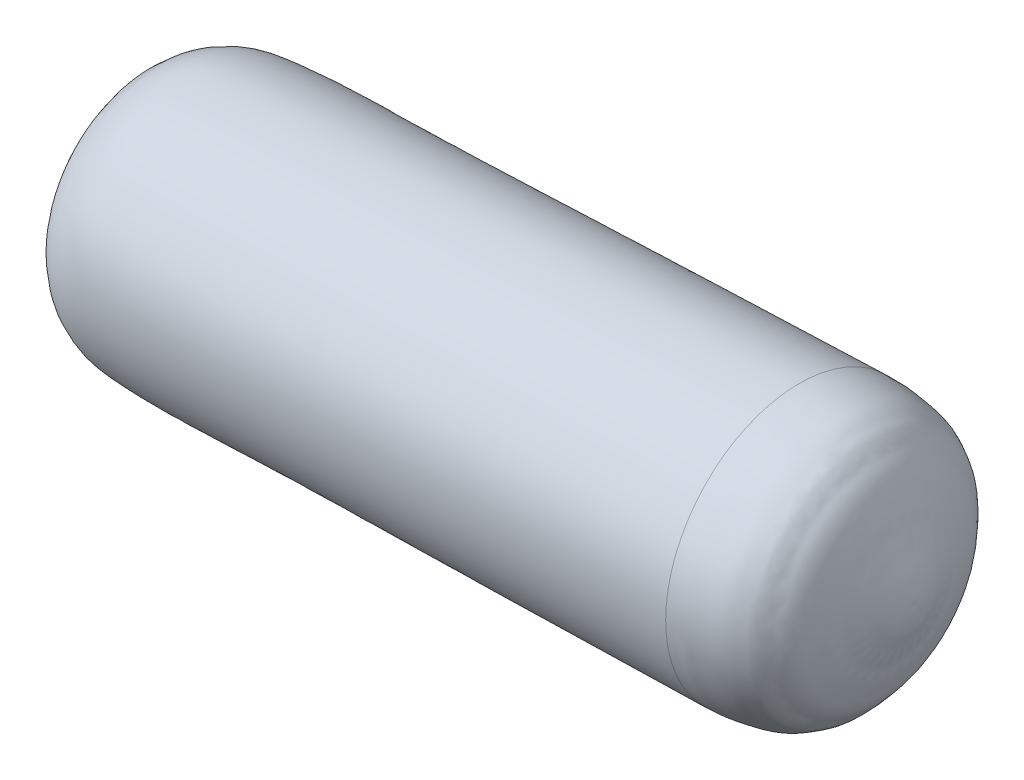
SolidWorks part; units mm, degrees
ref_plane "Front Plane" through (0, 0, 0) normal (0, 0, 1) x (1, 0, 0)
ref_plane "Top Plane" through (0, 0, 0) normal (0, 1, 0) x (1, 0, 0)
ref_plane "Right Plane" through (0, 0, 0) normal (1, 0, 0) x (0, 0, -1)
ref_plane "Plane1" through (0.0212, 0, 0.632) normal (-0.0336, 0, -0.9994) x (0, -1, 0)
sketch "Sketch1" plane through (0.0212, 0, 0.632) normal (-0.0336, 0, -0.9994) x (0, -1, 0)
  line L0 (-0.105, -0.3731) -> (-0.105, 0.4073)
  line L1 (-0.105, 0.4073) -> (-0.1384, 0.4086)
  line L2 (-0.105, -0.373) -> (-0.105, 0.4077) construction
  spline S0 degree 3 poles (-0.105, -0.3731) (-0.1098, -0.3739) (-0.1183, -0.3722) (-0.1297, -0.3706) (-0.1382, -0.3668) (-0.1456, -0.3641) (-0.153, -0.362) (-0.1612, -0.3578) (-0.1715, -0.3562) (-0.1815, -0.3515) (-0.1908, -0.3484) (-0.1991, -0.3444) (-0.206, -0.3397) (-0.2107, -0.3348) (-0.2151, -0.3318) (-0.2184, -0.3286) (-0.2223, -0.3248) (-0.2253, -0.3192) (-0.2285, -0.314) (-0.2315, -0.3078) (-0.2335, -0.2999) (-0.2349, -0.2912) (-0.236, -0.2829) (-0.2374, -0.2756) (-0.2372, -0.2677) (-0.2377, -0.262) (-0.2377, -0.2588) knots 0 0 0 0 0.072947 0.12902 0.173642 0.213636 0.247594 0.290001 0.351653 0.40388 0.45607 0.50112 0.542111 0.582547 0.602392 0.62235 0.652552 0.684276 0.716975 0.746536 0.788272 0.839552 0.880064 0.914245 0.951736 1 1 1 1
  spline S1 degree 3 poles (-0.1384, 0.4086) (-0.1362, 0.4053) (-0.145, 0.3964) (-0.1603, 0.3918) (-0.1776, 0.3822) (-0.1896, 0.3758) (-0.2012, 0.3694) (-0.2091, 0.3634) (-0.2152, 0.3561) (-0.2207, 0.3495) (-0.2238, 0.3428) (-0.2268, 0.3365) (-0.2298, 0.3287) (-0.2318, 0.3187) (-0.2331, 0.3065) (-0.2343, 0.2892) (-0.2353, 0.2664) (-0.2357, 0.2305) (-0.2348, 0.1609) (-0.2355, 0.0642) (-0.2365, -0.0476) (-0.237, -0.1341) (-0.2374, -0.2034) (-0.2374, -0.2396) (-0.2377, -0.2588) knots 0 0 0 0 0.01072 0.049534 0.066049 0.093708 0.106676 0.121341 0.134878 0.146949 0.157191 0.165283 0.176645 0.191943 0.207773 0.22836 0.264583 0.30344 0.378942 0.556453 0.709285 0.848169 0.919272 1 1 1 1
revolve "Revolve1" add sketch "Sketch1" angle 360 about L2 reverse direction yes
